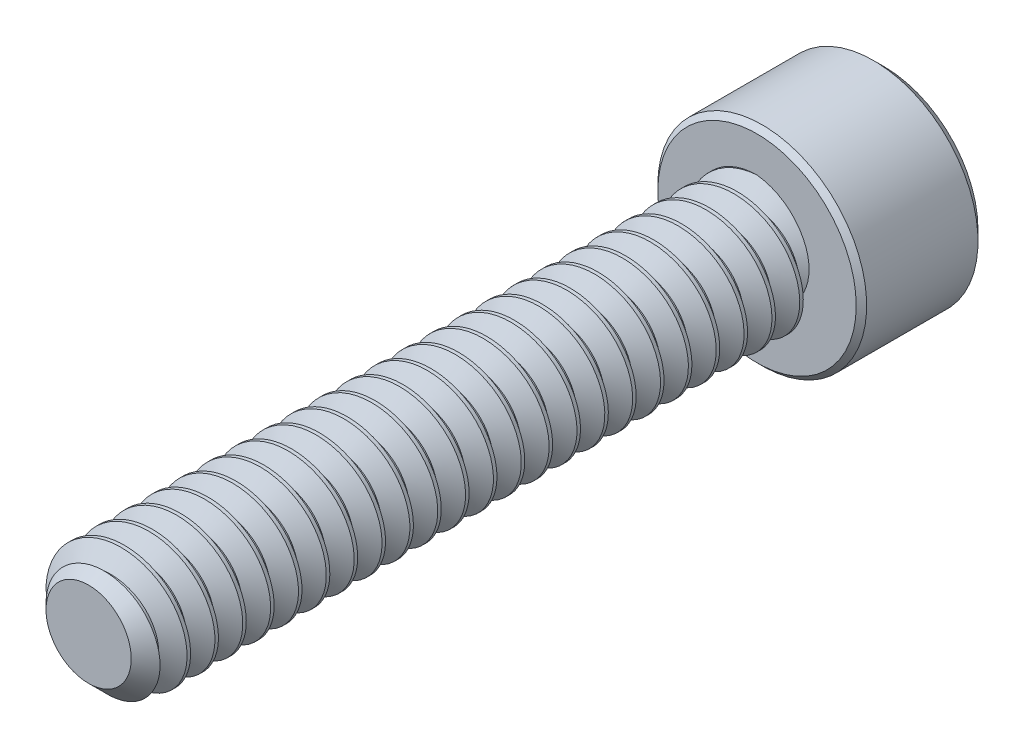
SolidWorks part; units mm, degrees
material "AISI 304"
ref_plane "Front Plane" through (0, 0, 0) normal (0, 0, 1) x (1, 0, 0)
ref_plane "Top Plane" through (0, 0, 0) normal (0, 1, 0) x (1, 0, 0)
ref_plane "Right Plane" through (0, 0, 0) normal (1, 0, 0) x (0, 0, -1)
sketch "Sketch0" plane through (0, 0, 0) normal (1, 0, 0) x (0, 0, -1)
  line L0 (0, 0) -> (25.4, 0) construction
  point P2 (30.226, 0)
  point P4 (0, 0)
  dimension "D1" = 25.4
  dimension "D2" = 4.826
  dimension "Min Thread" = 0
sketch "Sketch1" plane through (0, 0, 0) normal (0, 0, 1) x (1, 0, 0)
  circle A0 centre (0, 0) radius 2.413
  dimension "OD" = 4.826
extrude "Extrude1" add sketch "Sketch1" against normal blind 25.4
sketch "Sketch2" plane through (0, 0, 0) normal (0, 0, 1) x (1, 0, 0)
  circle A0 centre (0, 0) radius 2.413 construction
  circle A1 centre (0, 0) radius 2.413
curve "Helix/Spiral1" pitch 1.0583 height 26.4583 turns 25 parameters "pitch"=1.0583
chamfer "Chamfer3" distance 0.7937 angle 45 1 edges at (2.413, 0, 0)
sketch "Sketch3" plane through (0, 0, 0) normal (1, 0, 0) x (0, 0, -1)
  line L0 (-0.926, 2.413) -> (-0.5292, 1.7256)
  line L1 (-0.5292, 1.7256) -> (-0.3969, 1.7256)
  line L2 (-0.3969, 1.7256) -> (0, 2.413)
  line L3 (-0.926, 2.413) -> (0, 2.413)
  line L4 (-0.463, 2.413) -> (-0.463, 1.7256) construction
  line L5 (-0.7276, 2.0693) -> (-0.1984, 2.0693) construction
  line L6 (0, 2.413) -> (0, -2.413) construction
  dimension "D1" = 0.1323
  dimension "D2" = 0.5292
  dimension "D3" = 60
sweep "Cut-Sweep1" cut profiles "Sketch3" path "Helix/Spiral1"
sketch "Sketch5" plane through (0, 0, 0) normal (1, 0, 0) x (0, 0, -1)
  line L0 (25.4, -1.7471) -> (25.4, 1.7217) construction
  line L1 (25.4, 2.413) -> (0, 2.413)
  line L2 (25.4, 2.413) -> (25.4, 0)
  line L3 (25.4, 0) -> (-0.8783, 0)
  line L4 (0, 0) -> (25.4, 0) construction
  line L5 (0, 2.413) -> (-0.8783, 0)
  line L6 (0, 0) -> (27.94, 0) construction
  dimension "D1" = 70
  dimension "D3" = 2.54
revolve "partially thread" [suppressed] add sketch "Sketch5" angle 360 about L6
sketch "Sketch6" plane through (0, 0, -25.4) normal (0, 0, -1) x (-1, 0, 0)
  circle A0 centre (0, 0) radius 3.9688
  dimension "head dia" = 7.9375
extrude "Extrude2" add sketch "Sketch6" along normal blind 4.826
sketch "Sketch7" plane through (0, 0, -30.226) normal (0, 0, -1) x (-1, 0, 0)
  line L1 (0, 2.2914) -> (-1.9844, 1.1457)
  line L2 (-1.9844, 1.1457) -> (-1.9844, -1.1457)
  line L3 (-1.9844, -1.1457) -> (0, -2.2914)
  line L4 (0, -2.2914) -> (1.9844, -1.1457)
  line L5 (1.9844, -1.1457) -> (1.9844, 1.1457)
  line L6 (1.9844, 1.1457) -> (0, 2.2914)
  circle A0 centre (0, 0) radius 1.9844 construction
  dimension "hex dia" = 3.9688
extrude "Cut-Extrude1" cut sketch "Sketch7" against normal blind 2.9766
sketch "Sketch8" plane through (0, 0, -30.226) normal (0, 0, -1) x (-1, 0, 0)
  circle A0 centre (0, 0) radius 2.2914
extrude "Cut-Extrude2" cut sketch "Sketch8" against normal through all draft 45
chamfer "Chamfer1" distance 0.3969 angle 45 1 edges at (-3.9688, 0, -30.226)
chamfer "Chamfer2" distance 0.1984 angle 45 1 edges at (-3.9688, 0, -25.4)
sketch "Sketch9" plane through (0, 0, 0) normal (1, 0, 0) x (0, 0, -1)
  line L0 (0, 2.413) -> (0, -2.413) construction
  line L1 (2.6458, 2.413) -> (2.6458, -2.413) construction
  line L2 (30.226, 3.9688) -> (30.226, -3.9688) construction
  line L3 (25.4, 3.9688) -> (25.4, -3.9688) construction
  line L4 (25.4, 3.7703) -> (25.4, -3.7703) construction
  line L5 (30.226, -3.5719) -> (30.226, 3.5719) construction
  line L6 (25.4, -3.9688) -> (25.4, 3.9688) construction
  line L7 (0, 1.6193) -> (0, -1.6193) construction
  line L8 (-0.926, 2.413) -> (0, 2.413) construction
  line L9 (2.6458, 0) -> (0, 0) construction
  dimension "D1" = 2.6458
equation "\"D3@Helix/Spiral1\" = \"screw length@Extrude1\"+\"pitch@Helix/Spiral1\""
equation "\"D1@Sketch3\" = \"pitch@Helix/Spiral1\"*.125"
equation "\"D2@Sketch3\" = \"pitch@Helix/Spiral1\"*.5"
equation "\"D1@Cut-Extrude1\" = \"hex dia@Sketch7\"*.75"
equation "\"D1@Chamfer1\" = \"head dia@Sketch6\"*.05"
equation "\"D1@Sketch9\" = \"pitch@Helix/Spiral1\"*2.50"
equation "\"D1@Chamfer2\" = \"D1@Chamfer1\"/2"
equation "\"D1@Chamfer3\" = \"pitch@Helix/Spiral1\"*.750"
equation "\"D1@Sketch0\" = \"screw length@Extrude1\""
equation "\"D2@Sketch0\" = \"head depth@Extrude2\""
